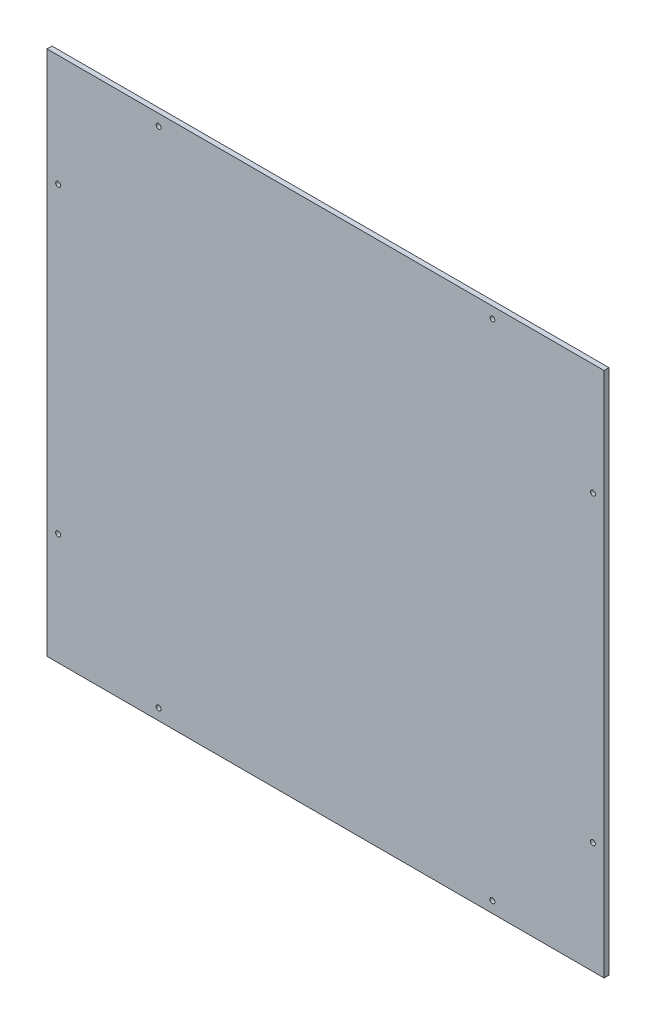
SolidWorks part; units mm, degrees
material "Acrilico (impatto medio-alto)"
ref_plane "Piano frontale" through (0, 0, 0) normal (0, 0, 1) x (1, 0, 0)
ref_plane "Piano superiore" through (0, 0, 0) normal (0, 1, 0) x (1, 0, 0)
ref_plane "Piano destro" through (0, 0, 0) normal (1, 0, 0) x (0, 0, -1)
sketch "Schizzo1" plane through (0, 0, 0) normal (0, 0, 1) x (1, 0, 0)
  line L0 (-224.5, 351.6275) -> (-224.5, -66.2585) construction
  line L1 (0, 0) -> (-449, 0)
  line L2 (0, 0) -> (0, 424)
  line L3 (0, 424) -> (-449, 424)
  line L4 (-449, 0) -> (-449, 424)
  line L5 (-387.9788, 212) -> (120.8821, 212) construction
  circle A0 centre (-90, 415) radius 2
  circle A1 centre (-9, 334) radius 2
  circle A2 centre (-359, 415) radius 2
  circle A3 centre (-440, 334) radius 2
  circle A4 centre (-359, 9) radius 2
  circle A5 centre (-440, 90) radius 2
  circle A6 centre (-9, 90) radius 2
  circle A7 centre (-90, 9) radius 2
  point P9 (-224.5, 212)
  dimension "D3" = 4
  dimension "D1" = 449
  dimension "314" = 424
  dimension "D4" = 9
  dimension "D5" = 90
  dimension "D6" = 9
  dimension "D7" = 90
extrude "Estrusione-Estrusione1" add sketch "Schizzo1" along normal blind 4
